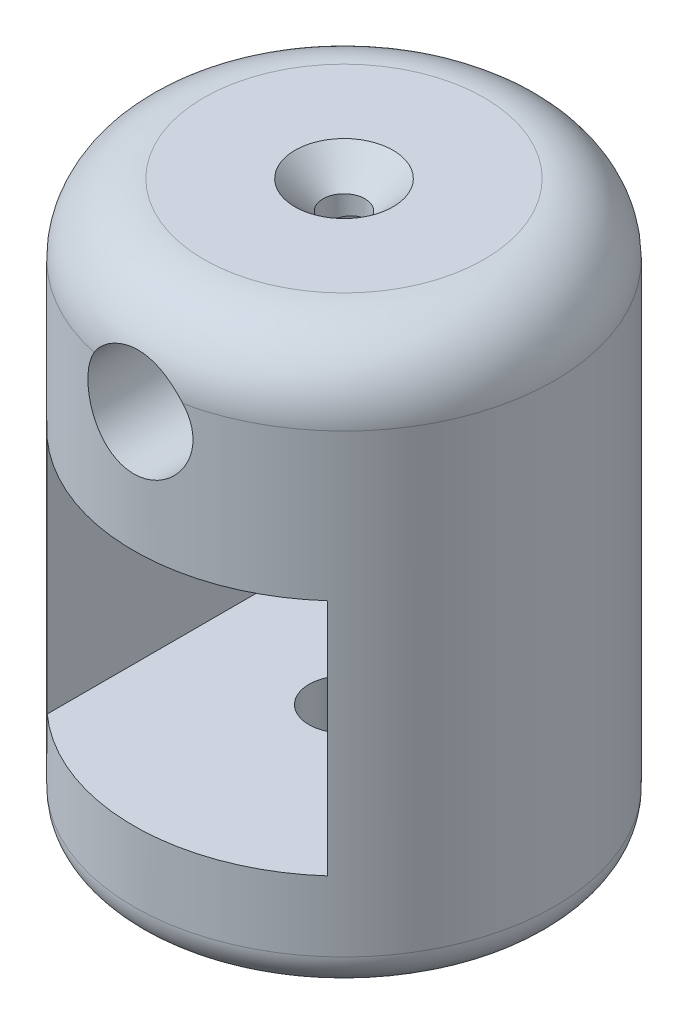
SolidWorks part; units mm, degrees
ref_plane "Front Plane" through (0, 0, 0) normal (0, 0, 1) x (1, 0, 0)
ref_plane "Top Plane" through (0, 0, 0) normal (0, 1, 0) x (1, 0, 0)
ref_plane "Right Plane" through (0, 0, 0) normal (1, 0, 0) x (0, 0, -1)
sketch "Sketch1" plane through (0, 0, 0) normal (0, 1, 0) x (1, 0, 0)
  circle A0 centre (0, 0) radius 15
  dimension "D1" = 30
extrude "Boss-Extrude1" add sketch "Sketch1" along normal blind 40
sketch "Sketch2" plane through (0, 0, 0) normal (0, 0, 1) x (1, 0, 0)
  line L0 (0, 0) -> (0, 7.5)
  line L1 (0, 7.5) -> (-10, 7.5)
  line L2 (-10, 7.5) -> (-10, 24.5)
  line L3 (-10, 24.5) -> (10, 24.5)
  line L4 (10, 24.5) -> (10, 7.5)
  line L5 (10, 7.5) -> (0, 7.5)
  line L6 (0, 40) -> (0, 33)
  line L7 (15, 40) -> (-15, 40) construction
  circle A0 centre (0, 33) radius 3.75
  dimension "D5" = 7.5
  dimension "D1" = 7.5
  dimension "D2" = 10
  dimension "D3" = 10
  dimension "D4" = 17
  dimension "D6" = 7
extrude "Cut-Extrude1" cut sketch "Sketch2" against normal blind 40 and the other way blind 40 contours L5 L4 L3 L2 L1 | A0 region at (0, 16, 0)
sketch "Sketch4" plane through (0, 40, 0) normal (0, 1, 0) x (1, 0, 0)
  circle A0 centre (0, 0) radius 1.5
  dimension "D1" = 3
extrude "Cut-Extrude2" cut sketch "Sketch4" against normal blind 8
sketch "Sketch5" plane through (0, 0, 0) normal (0, -1, 0) x (1, 0, 0)
  circle A0 centre (0, 0) radius 2.5
  dimension "D1" = 5
extrude "Cut-Extrude3" cut sketch "Sketch5" against normal blind 8
fillet "Fillet1" radius 5 1 edges at (0, 40, 15)
chamfer "Chamfer1" distance 2 angle 45 1 edges at (0, 40, 1.5)
fillet "Fillet2" radius 2.5 1 edges at (0, 0, 15)
